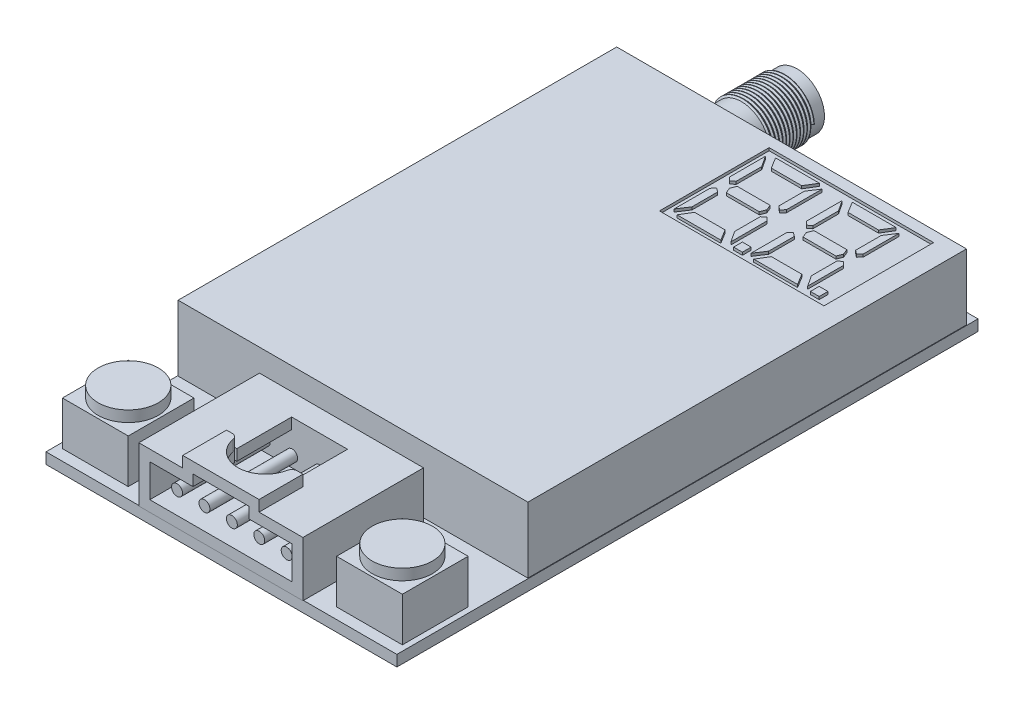
SolidWorks part; units mm, degrees
ref_plane "Ön Düzlem" through (0, 0, 0) normal (0, 0, 1) x (1, 0, 0)
ref_plane "Üst Düzlem" through (0, 0, 0) normal (0, 1, 0) x (1, 0, 0)
ref_plane "Sağ Düzlem" through (0, 0, 0) normal (1, 0, 0) x (0, 0, -1)
sketch "Çizim1" plane through (0, 0, 0) normal (0, 1, 0) x (1, 0, 0)
  line L1 (16, -26.5) -> (-16, -26.5)
  line L2 (16, -26.5) -> (16, 26.5)
  line L3 (16, 26.5) -> (-16, 26.5)
  line L4 (-16, -26.5) -> (-16, 26.5)
  line L5 (16, -26.5) -> (-16, 26.5) construction
  line L6 (16, 26.5) -> (-16, -26.5) construction
  point P0 (0, 0)
  dimension "D1" = 32
  dimension "D2" = 53
extrude "Yükseklik-Ekstrüzyon1" add sketch "Çizim1" along normal blind 1
sketch "Çizim2" plane through (0, 1, 0) normal (0, 1, 0) x (1, 0, 0)
  line L1 (-15.95, 25.5) -> (15.95, 25.5)
  line L2 (-15.95, 25.5) -> (-15.95, -14.5)
  line L3 (-15.95, -14.5) -> (15.95, -14.5)
  line L4 (15.95, 25.5) -> (15.95, -14.5)
  line L6 (16, 26.5) -> (-16, 26.5) construction
  line L7 (-16, 26.5) -> (-16, -26.5) construction
  line L8 (16, -26.5) -> (16, 26.5) construction
  point P4 (-15.7408, 25.5127)
  point P5 (-15.8816, -14.4557)
  point P6 (0, 0)
  point P7 (14.844, 25.2173)
  point P9 (16, -14.4476)
  point P10 (0, 0)
  point P11 (15.7685, -14.5472)
  dimension "D1" = 1
  dimension "D2" = 0.05
  dimension "D3" = 0.05
  dimension "D4" = 40
extrude "Yükseklik-Ekstrüzyon2" add sketch "Çizim2" along normal blind 6 separate body
sketch "Çizim3" plane through (0, 1, 0) normal (0, 1, 0) x (1, 0, 0)
  line L0 (16, -26.5) -> (16, 26.5) construction
  line L1 (15.5, -25.5) -> (9.5, -25.5)
  line L2 (15.5, -25.5) -> (15.5, -19.5)
  line L3 (15.5, -19.5) -> (9.5, -19.5)
  line L4 (9.5, -25.5) -> (9.5, -19.5)
  line L5 (15.5, -25.5) -> (9.5, -19.5) construction
  line L6 (15.5, -19.5) -> (9.5, -25.5) construction
  line L7 (-16, -26.5) -> (16, -26.5) construction
  line L8 (0, 0) -> (0, -34.6384) construction
  line L9 (-15.5, -25.5) -> (-9.5, -25.5)
  line L10 (-15.5, -25.5) -> (-15.5, -19.5)
  line L11 (-15.5, -19.5) -> (-9.5, -25.5) construction
  line L12 (-15.5, -25.5) -> (-9.5, -19.5) construction
  line L13 (-15.5, -19.5) -> (-9.5, -19.5)
  line L14 (-9.5, -25.5) -> (-9.5, -19.5)
  point P0 (12.5, -22.5)
  dimension "D1" = 0.5
  dimension "D2" = 1
  dimension "D3" = 6
extrude "Yükseklik-Ekstrüzyon5" add sketch "Çizim3" along normal blind 4
sketch "Çizim7" plane through (0, 5, 0) normal (0, 1, 0) x (1, 0, 0)
  line L0 (-12.5, -19.5) -> (-12.5, -25.5) construction
  line L1 (-9.5, -19.5) -> (-15.5, -19.5) construction
  line L2 (-15.5, -25.5) -> (-9.5, -25.5) construction
  line L3 (0, 0) -> (0, -43.4211) construction
  circle A0 centre (-12.5, -22.5) radius 2.75
  circle A1 centre (12.5, -22.5) radius 2.75
  dimension "D1" = 5.5
extrude "Yükseklik-Ekstrüzyon6" add sketch "Çizim7" along normal blind 1
sketch "Çizim11" plane through (0, 0, 26.5) normal (0, 0, 1) x (1, 0, 0)
  line L0 (-7.481, 1) -> (7.481, 1)
  line L1 (7.481, 1) -> (7.481, 6)
  line L2 (-7.481, 6) -> (7.481, 6)
  line L6 (-7.481, 1) -> (-7.481, 6)
  point P3 (0, 1)
  point P11 (0, 7)
  dimension "D1" = 5
extrude "Yükseklik-Ekstrüzyon8" add sketch "Çizim11" against normal blind 11 from offset 0.05 separate body
sketch "Çizim15" plane through (0, 0, 26.55) normal (0, 0, 1) x (1, 0, 0)
  line L0 (0, 6) -> (3.481, 6)
  line L1 (7.481, 6) -> (-7.481, 6) construction
  line L2 (3.481, 6) -> (3.481, 7)
  line L3 (3.481, 7) -> (-3.481, 7)
  line L4 (-3.481, 7) -> (-3.481, 6)
  line L5 (-3.481, 6) -> (0, 6)
  dimension "D1" = 4
  dimension "D2" = 1
extrude "Yükseklik-Ekstrüzyon9" add sketch "Çizim15" against normal blind 4
sketch "Çizim16" plane through (0, 7, 0) normal (0, 1, 0) x (1, 0, 0)
  line L0 (2.958, -22.55) -> (2, -22.55)
  line L1 (-2, -22.55) -> (-2, -17.55)
  line L2 (-2, -17.55) -> (2, -17.55)
  line L3 (-2, -22.55) -> (-2.958, -22.55)
  line L4 (3.481, -26.55) -> (-3.481, -26.55) construction
  line L5 (2, -17.55) -> (2, -22.55)
  line L6 (3.481, -22.55) -> (-3.481, -22.55) construction
  arc A0 (-2.4668, -22.9569) -> (-2.958, -22.55) centre (-2.958, -23.05) ccw
  arc A1 (-2.4668, -22.9569) -> (2.4668, -22.9569) centre (0, -22.4893) ccw
  arc A2 (2.4668, -22.9569) -> (2.958, -22.55) centre (2.958, -23.05) cw
  point P2 (0, -26.55)
  point P3 (0, -20.2825)
  point P10 (0, -25)
  dimension "D1" = 0.5
  dimension "D4" = 5
  dimension "D5" = 4
extrude "Kes-Ekstrüzyon2" cut sketch "Çizim16" against normal blind 4
sketch "Çizim12" plane through (0, 0, 26.55) normal (0, 0, 1) x (1, 0, 0)
  line L0 (-6.481, 2) -> (6.481, 2)
  line L1 (6.481, 2) -> (6.481, 5)
  line L2 (6.481, 5) -> (2.5478, 5)
  line L3 (2.5478, 5) -> (2.5478, 6.0048)
  line L4 (2.5478, 6.0048) -> (-2.5478, 6.0048)
  line L10 (0, 1) -> (0, 16.1084) construction
  line L11 (-6.481, 2) -> (-6.481, 5)
  line L12 (-2.5478, 5) -> (-2.5478, 6.0048)
  line L13 (-6.481, 5) -> (-2.5478, 5)
  point P21 (0, 2)
  point P22 (0, 6.0048)
extrude "Kes-Ekstrüzyon1" cut sketch "Çizim12" against normal blind 9
sketch "Çizim18" plane through (0, 0, -26.5) normal (0, 0, -1) x (-1, 0, 0)
  line L0 (16, 1) -> (16, 0) construction
  line L1 (13, -2.5) -> (7, -2.5)
  line L2 (13, -2.5) -> (13, 3.5)
  line L3 (13, 3.5) -> (7, 3.5)
  line L4 (7, -2.5) -> (7, 3.5)
  line L5 (13, -2.5) -> (7, 3.5) construction
  line L6 (13, 3.5) -> (7, -2.5) construction
  point P0 (10, 0.5)
  point P7 (16, 0.5)
  point P8 (13, 0.5)
  dimension "D1" = 6
  dimension "D2" = 3
extrude "Yükseklik-Ekstrüzyon11" add sketch "Çizim18" along normal blind 1.5
sketch "Çizim19" plane through (0, 0, -28) normal (0, 0, -1) x (-1, 0, 0)
  line L0 (7, 0.5) -> (13, 0.5) construction
  line L1 (7, 3.5) -> (7, -2.5) construction
  line L2 (13, -2.5) -> (13, 3.5) construction
  circle A0 centre (10, 0.5) radius 2.5
  dimension "D1" = 5
extrude "Yükseklik-Ekstrüzyon12" add sketch "Çizim19" along normal blind 8
sketch "Çizim20" plane through (0, 0, -36) normal (0, 0, -1) x (-1, 0, 0)
  circle A0 centre (10, 0.5) radius 2.25
  circle A1 centre (10, 0.5) radius 0.5
  dimension "D1" = 4.5
  dimension "D2" = 1
extrude "Kes-Ekstrüzyon3" cut sketch "Çizim20" against normal blind 3
thread "MinColWidth_OnTracking1" pitch 0.3175 method extrude profile "HeaderRowsCount1" start angle 0, offset 1, length 4, pitch 0.3175, diameter 5
ref_plane "Düzlem1" through (-7.5, 0.5, -35) normal (0, -1, 0) x (1, 0, 0)
sketch "HeaderRowsCount1" plane through (-7.5, 0.5, -35) normal (0, -1, 0) x (1, 0, 0)
  line L0 (0, 0) -> (0, 0.3175) construction
  line L1 (0, 0) -> (0.1719, 0.0992)
  line L2 (0.1719, 0.0992) -> (0.1719, 0.1389)
  line L3 (0.1719, 0.1389) -> (0, 0.2381)
  line L4 (0.1719, 0.1191) -> (0, 0.1191) construction
  line L11 (0, 0) -> (0, 0.2381)
  point P2 (0, 0)
  dimension "Pitch" = 0.3175
  dimension "Profile_Angle" = 60
  dimension "Profile_Land" = 0.0397
  dimension "Profile_Height" = 0.1719
sketch "Çizim25" plane through (0, 7, 0) normal (0, 1, 0) x (1, 0, 0)
  line L0 (15.95, 25.5) -> (-15.95, 25.5) construction
  line L1 (13.95, 24.5) -> (-1.05, 24.5)
  line L2 (13.95, 24.5) -> (13.95, 14.5)
  line L3 (13.95, 14.5) -> (-1.05, 14.5)
  line L4 (-1.05, 24.5) -> (-1.05, 14.5)
  line L5 (15.95, -14.5) -> (15.95, 25.5) construction
  dimension "D1" = 1
  dimension "D2" = 2
  dimension "D3" = 15
  dimension "D4" = 10
extrude "Kes-Ekstrüzyon4" cut sketch "Çizim25" against normal blind 0.25
sketch "Çizim27" plane through (0, 6.75, 0) normal (0, 1, 0) x (1, 0, 0)
  line L0 (0.0534, 14.9926) -> (4.0534, 14.9926)
  line L2 (3.442, 15.9926) -> (0.6648, 15.9926)
  line L3 (0.6648, 15.9926) -> (0.0534, 14.9926)
  line L4 (0.107, 16.3055) -> (-0.5365, 15.3258)
  line L5 (-0.5365, 15.3258) -> (-0.5365, 18.5945)
  line L6 (0.107, 16.3055) -> (0.107, 18.6397)
  line L7 (-0.5365, 18.5945) -> (-0.2353, 18.9027)
  line L8 (-0.2353, 18.9027) -> (0.107, 18.6397)
  line L9 (0.6648, 18.9878) -> (3.442, 18.9878)
  line L10 (0.5534, 19.9878) -> (3.5534, 19.9878)
  line L11 (5.1894, 15.8242) -> (5.9894, 15.8242)
  line L12 (5.1894, 15.8242) -> (5.1894, 15.0242)
  line L13 (5.1894, 15.0242) -> (5.9894, 15.0242)
  line L14 (0.3553, 19.4878) -> (0.5534, 19.9878)
  line L15 (5.9894, 15.8242) -> (5.9894, 15.0242)
  line L16 (3.7515, 19.4878) -> (3.5534, 19.9878)
  line L18 (4.3421, 18.9027) -> (3.9997, 18.6397)
  line L19 (4.6432, 18.5945) -> (4.3421, 18.9027)
  line L20 (3.9997, 16.3055) -> (3.9997, 18.6397)
  line L21 (4.6432, 15.3258) -> (4.6432, 18.5945)
  line L22 (3.9997, 16.3055) -> (4.6432, 15.3258)
  line L23 (3.442, 15.9926) -> (4.0534, 14.9926)
  line L24 (0.6648, 15.9926) -> (3.442, 15.9926)
  line L26 (4.0534, 14.9926) -> (0.0534, 14.9926)
  line L27 (4.0534, 23.983) -> (0.0534, 23.983)
  line L28 (7.0534, 14.9926) -> (11.0534, 14.9926)
  line L29 (0.6648, 22.983) -> (3.442, 22.983)
  line L30 (3.442, 22.983) -> (4.0534, 23.983)
  line L31 (3.9997, 22.6702) -> (4.6432, 23.6498)
  line L32 (4.6432, 23.6498) -> (4.6432, 20.3812)
  line L33 (3.9997, 22.6702) -> (3.9997, 20.336)
  line L34 (4.6432, 20.3812) -> (4.3421, 20.073)
  line L35 (4.3421, 20.073) -> (3.9997, 20.336)
  line L36 (10.442, 15.9926) -> (7.6648, 15.9926)
  line L37 (3.7515, 19.4878) -> (3.5534, 18.9878)
  line L38 (0.3553, 19.4878) -> (0.5534, 18.9878)
  line L39 (7.6648, 15.9926) -> (7.0534, 14.9926)
  line L40 (0.5534, 18.9878) -> (3.5534, 18.9878)
  line L41 (0.6648, 19.9878) -> (3.442, 19.9878)
  line L42 (-0.2353, 20.073) -> (0.107, 20.336)
  line L43 (-0.5365, 20.3812) -> (-0.2353, 20.073)
  line L44 (0.107, 22.6702) -> (0.107, 20.336)
  line L45 (-0.5365, 23.6498) -> (-0.5365, 20.3812)
  line L46 (0.107, 22.6702) -> (-0.5365, 23.6498)
  line L47 (0.6648, 22.983) -> (0.0534, 23.983)
  line L48 (3.442, 22.983) -> (0.6648, 22.983)
  line L49 (7.107, 16.3055) -> (6.4635, 15.3258)
  line L50 (0.0534, 23.983) -> (4.0534, 23.983)
  line L51 (6.4635, 15.3258) -> (6.4635, 18.5945)
  line L52 (7.107, 16.3055) -> (7.107, 18.6397)
  line L53 (6.4635, 18.5945) -> (6.7647, 18.9027)
  line L54 (6.7647, 18.9027) -> (7.107, 18.6397)
  line L55 (7.6648, 18.9878) -> (10.442, 18.9878)
  line L56 (7.5534, 19.9878) -> (10.5534, 19.9878)
  line L57 (12.1894, 15.8242) -> (12.9894, 15.8242)
  line L58 (12.1894, 15.8242) -> (12.1894, 15.0242)
  line L59 (12.1894, 15.0242) -> (12.9894, 15.0242)
  line L60 (7.3553, 19.4878) -> (7.5534, 19.9878)
  line L61 (12.9894, 15.8242) -> (12.9894, 15.0242)
  line L62 (10.7515, 19.4878) -> (10.5534, 19.9878)
  line L63 (11.3421, 18.9027) -> (10.9997, 18.6397)
  line L64 (11.6432, 18.5945) -> (11.3421, 18.9027)
  line L65 (10.9997, 16.3055) -> (10.9997, 18.6397)
  line L66 (11.6432, 15.3258) -> (11.6432, 18.5945)
  line L67 (10.9997, 16.3055) -> (11.6432, 15.3258)
  line L68 (10.442, 15.9926) -> (11.0534, 14.9926)
  line L69 (7.6648, 15.9926) -> (10.442, 15.9926)
  line L70 (11.0534, 14.9926) -> (7.0534, 14.9926)
  line L71 (11.0534, 23.983) -> (7.0534, 23.983)
  line L72 (7.6648, 22.983) -> (10.442, 22.983)
  line L73 (10.442, 22.983) -> (11.0534, 23.983)
  line L74 (10.9997, 22.6702) -> (11.6432, 23.6498)
  line L75 (11.6432, 23.6498) -> (11.6432, 20.3812)
  line L76 (10.9997, 22.6702) -> (10.9997, 20.336)
  line L77 (11.6432, 20.3812) -> (11.3421, 20.073)
  line L78 (11.3421, 20.073) -> (10.9997, 20.336)
  line L79 (10.7515, 19.4878) -> (10.5534, 18.9878)
  line L80 (7.3553, 19.4878) -> (7.5534, 18.9878)
  line L81 (7.5534, 18.9878) -> (10.5534, 18.9878)
  line L82 (7.6648, 19.9878) -> (10.442, 19.9878)
  line L83 (6.7647, 20.073) -> (7.107, 20.336)
  line L84 (6.4635, 20.3812) -> (6.7647, 20.073)
  line L85 (7.107, 22.6702) -> (7.107, 20.336)
  line L86 (6.4635, 23.6498) -> (6.4635, 20.3812)
  line L87 (7.107, 22.6702) -> (6.4635, 23.6498)
  line L88 (7.6648, 22.983) -> (7.0534, 23.983)
  line L89 (10.442, 22.983) -> (7.6648, 22.983)
  line L90 (7.0534, 23.983) -> (11.0534, 23.983)
  point P2 (2.0534, 15.9926)
  point P5 (2.0534, 14.9926)
  point P15 (2.0534, 18.9878)
  point P16 (2.0534, 19.9878)
  point P64 (2.0534, 19.4878)
  point P87 (9.0534, 19.4878)
  dimension "D1" = 4
  dimension "D2" = 0.8
  dimension "D3" = 1
  dimension "D4" = 2
  dimension "D6" = 3
  dimension "D7" = 1
extrude "Yükseklik-Ekstrüzyon13" add sketch "Çizim27" along normal blind 0.25 contours L47 L29 L30 L27 | L35 L34 L32 L31 L33 | L38 L40 L9 L37 L16 L10 L14 | L44 L46 L45 L43 L42 | L8 L7 L5 L4 L6 | L23 L2 L3 L0 | L20 L22 L21 L19 L18 | L15 L11 L12 L13 | L54 L53 L51 L49 L52 | L80 L81 L55 L79 L62 L56 L60 | L85 L87 L86 L84 L83 | L88 L72 L73 L71 | L78 L77 L75 L74 L76 | L65 L67 L66 L64 L63 | L68 L36 L39 L28 | L61 L57 L58 L59 region at (2.0534, 6.75, -15.4625) region at (-0.2321, 6.75, -17.2757) region at (2.0534, 6.75, -19.4878) region at (5.5894, 6.75, -15.4242) region at (4.3388, 6.75, -17.2757) region at (2.0534, 6.75, -23.5131) region at (9.0534, 6.75, -15.4625) region at (4.3388, 6.75, -21.6999) region at (-0.2321, 6.75, -21.6999) region at (6.7679, 6.75, -17.2757) region at (9.0534, 6.75, -19.4878) region at (12.5894, 6.75, -15.4242) region at (11.3388, 6.75, -17.2757) region at (9.0534, 6.75, -23.5131) region at (11.3388, 6.75, -21.6999) region at (6.7679, 6.75, -21.6999)
sketch "Çizim28" plane through (0, 0, 17.55) normal (0, 0, 1) x (1, 0, 0)
  line L0 (-2.5478, 5) -> (2.5478, 5) construction
  line L1 (0, 5) -> (0, 1) construction
  line L2 (0, 3) -> (5, 3) construction
  line L3 (-5, 3) -> (5, 3) construction
  line L4 (5, 3) -> (2.5, 3) construction
  line L5 (2.5, 3) -> (0, 3) construction
  line L6 (0, 3) -> (-2.5, 3) construction
  line L7 (-2.5, 3) -> (-5, 3) construction
  line L8 (-7.481, 1) -> (7.481, 1) construction
  circle A0 centre (0, 3) radius 0.5
  circle A1 centre (2.5, 3) radius 0.5
  circle A2 centre (5, 3) radius 0.5
  circle A3 centre (-5, 3) radius 0.5
  circle A4 centre (-2.5, 3) radius 0.5
  point P16 (0, 3)
extrude "Yükseklik-Ekstrüzyon14" add sketch "Çizim28" along normal blind 8
